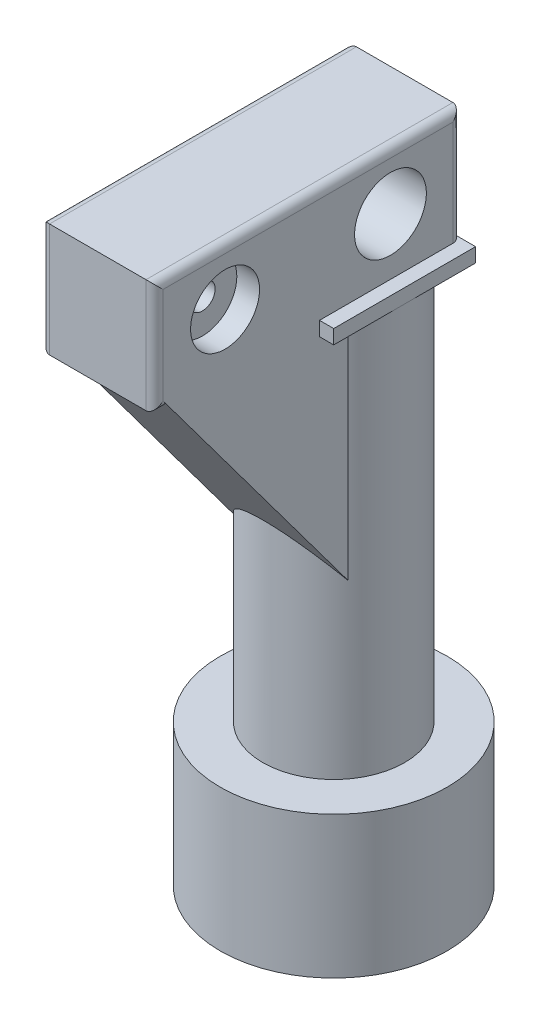
SolidWorks part; units mm, degrees
ref_plane "Alzado" through (0, 0, 0) normal (0, 0, 1) x (1, 0, 0)
ref_plane "Planta" through (0, 0, 0) normal (0, 1, 0) x (1, 0, 0)
ref_plane "Vista lateral" through (0, 0, 0) normal (1, 0, 0) x (0, 0, -1)
sketch "Croquis1" plane through (0, 0, 0) normal (0, 1, 0) x (1, 0, 0)
  circle A0 centre (0, 0) radius 40
  circle A1 centre (0, 0) radius 6
  dimension "D1" = 80
  dimension "D2" = 12
extrude "Saliente-Extruir1" add sketch "Croquis1" along normal blind 30
sketch "Croquis2" plane through (0, 0, 0) normal (0, -1, 0) x (1, 0, 0)
  circle A0 centre (0, 0) radius 40
  circle A1 centre (0, 0) radius 35.3
  circle A2 centre (0, 0) radius 40 construction
  dimension "D1" = 4.7
  dimension "D2" = 0
extrude "Saliente-Extruir2" add sketch "Croquis2" along normal blind 20
sketch "Croquis6" plane through (0, 0, 0) normal (0, -1, 0) x (1, 0, 0)
  line L1 (-3.4534, -6.2052) -> (3.6472, -6.0933)
  line L2 (3.6472, -6.0933) -> (7.1005, 0.1119)
  line L3 (7.1005, 0.1119) -> (3.4534, 6.2052)
  line L4 (3.4534, 6.2052) -> (-3.6472, 6.0933)
  line L5 (-3.6472, 6.0933) -> (-7.1005, -0.1119)
  line L6 (-7.1005, -0.1119) -> (-3.4534, -6.2052)
  circle A0 centre (0, 0) radius 6
  circle A1 centre (0, 0) radius 6.15 construction
  point P3 (5.2769, 3.1585)
  dimension "D1" = 12
  dimension "D2" = 12.3
extrude "Cortar-Extruir3" cut sketch "Croquis6" against normal blind 25
sketch "Croquis7" plane through (0, 30, 0) normal (0, 1, 0) x (1, 0, 0)
  circle A0 centre (0, 0) radius 25
  circle A1 centre (0, 0) radius 21
  dimension "D1" = 50
  dimension "D2" = 4
extrude "Saliente-Extruir3" add sketch "Croquis7" along normal blind 140
sketch "Croquis9" plane through (0, 170, 0) normal (0, 1, 0) x (1, 0, 0)
  line L1 (-25, 25) -> (25, 25)
  line L2 (-25, 25) -> (-25, -25)
  line L3 (-25, -25) -> (25, -25)
  line L4 (25, 25) -> (25, -25)
  circle A4 centre (0, 0) radius 6
  dimension "D1" = 50
  dimension "D2" = 25
  dimension "D3" = 25
  dimension "D4" = 50
extrude "Saliente-Extruir4" add sketch "Croquis9" along normal blind 5
sketch "Croquis17" plane through (0, 175, 0) normal (0, 1, 0) x (1, 0, 0)
  line L0 (25, 25) -> (-25, 25) construction
  line L1 (-20, 25) -> (20, 25)
  line L2 (-20, 25) -> (-20, -25)
  line L3 (-20, -25) -> (20, -25)
  line L4 (20, 25) -> (20, -25)
  line L5 (-25, -25) -> (25, -25) construction
  line L6 (-25, 25) -> (-25, -25) construction
  dimension "D1" = 40
  dimension "D2" = 5
extrude "Saliente-Extruir9" add sketch "Croquis17" along normal blind 40
sketch "Croquis18" plane through (-20, 0, 0) normal (-1, 0, 0) x (0, 0, 1)
  line L0 (-25, 175) -> (25, 175) construction
  line L1 (-25, 215) -> (83.1609, 215)
  line L2 (-25, 215) -> (-25, 175)
  line L3 (-25, 175) -> (83.1609, 175)
  line L4 (83.1609, 215) -> (83.1609, 175)
  line L5 (25, 215) -> (25, 175)
  line M3 (25, 175) -> (25, 215)
  dimension "D1" = 0
extrude "Saliente-Extruir10" add sketch "Croquis18" against normal blind 40 contours L4 L1 L3 M3 region at (-20, 195, 54.0805)
fillet "Redondeo1" radius 3 8 edges at (-20, 175, 54.0805) (-20, 195, 83.1609) (-20, 215, 29.0805) (-20, 195, -25) (20, 195, -25) (20, 175, 54.0805) (20, 195, 83.1609) (20, 215, 29.0805)
sketch "Croquis19" plane through (-20, 0, 0) normal (-1, 0, 0) x (0, 0, 1)
  line L0 (-25, 215) -> (83.1609, 215) construction
  line L2 (-25, 175) -> (-25, 215) construction
  circle A0 centre (0, 195) radius 12.65
  circle A1 centre (58.2965, 195) radius 4.5
  dimension "D1" = 25.3
  dimension "D2" = 20
  dimension "D4" = 9
  dimension "D3" = 25
extrude "Cortar-Extruir7" cut sketch "Croquis19" against normal blind 40
sketch "Croquis20" plane through (-20, 0, 0) normal (-1, 0, 0) x (0, 0, 1)
  circle A0 centre (58.2965, 195) radius 12.15
  dimension "D1" = 24.3
extrude "Cortar-Extruir8" cut sketch "Croquis20" against normal blind 8
sketch "Croquis21" plane through (20, 0, 0) normal (1, 0, 0) x (0, 0, -1)
  circle A0 centre (-58.2965, 195) radius 12.15
  dimension "D1" = 24.3
extrude "Cortar-Extruir9" cut sketch "Croquis21" against normal blind 8
sketch "Croquis22" plane through (20, 0, 0) normal (1, 0, 0) x (0, 0, -1)
  line L3 (-80.1609, 178) -> (-13.008, 178)
  line L4 (-13.008, 178) -> (-13.008, 87.9843)
  line L5 (-13.008, 87.9843) -> (-80.1609, 178)
  point P4 (-13.008, 87.9843)
extrude "Saliente-Extruir11" add sketch "Croquis22" against normal blind 40
